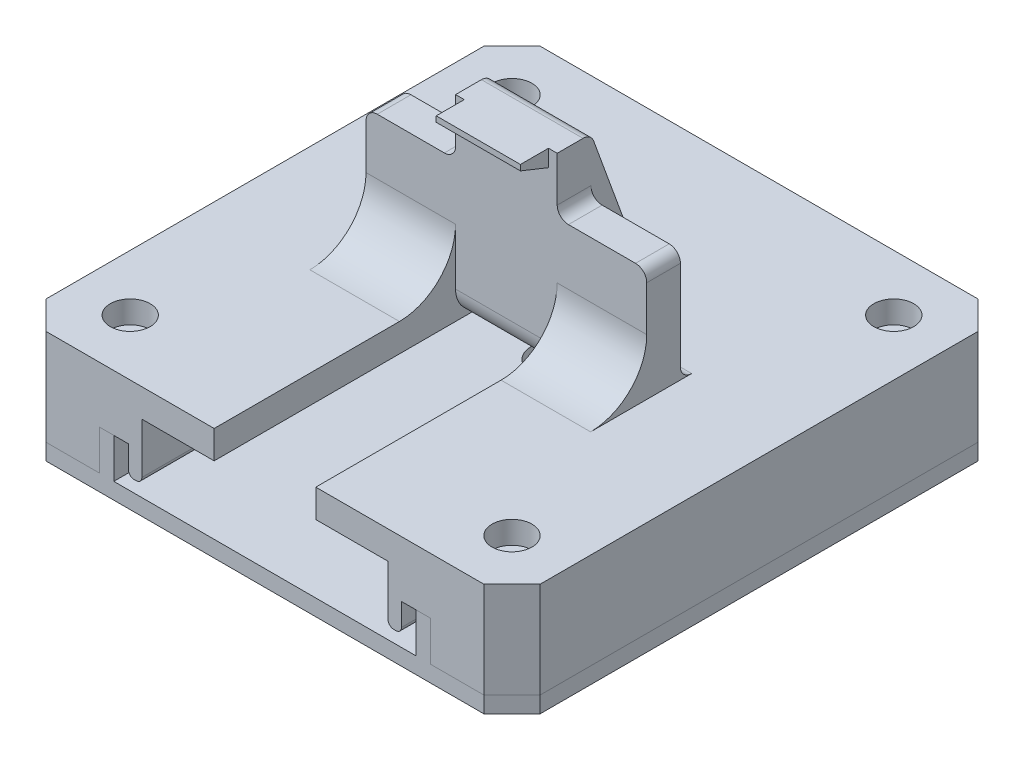
SolidWorks part; units mm, degrees
ref_plane "Piano frontale" through (0, 0, 0) normal (0, 0, 1) x (1, 0, 0)
ref_plane "Piano superiore" through (0, 0, 0) normal (0, 1, 0) x (1, 0, 0)
ref_plane "Piano destro" through (0, 0, 0) normal (1, 0, 0) x (0, 0, -1)
sketch "Schizzo2" plane through (0, 0, 0) normal (0, 1, 0) x (1, 0, 0)
  line L1 (-44, -44) -> (44, -44)
  line L2 (-44, -44) -> (-44, 44)
  line L3 (-44, 44) -> (44, 44)
  line L4 (44, -44) -> (44, 44)
  line L5 (-44, -44) -> (44, 44) construction
  line L6 (-44, 44) -> (44, -44) construction
  point P0 (0, 0)
  dimension "D1" = 88
  dimension "D2" = 88
extrude "Estrusione-Estrusione1" add sketch "Schizzo2" along normal blind 20
sketch "Sketch1" plane through (0, 0, 44) normal (0, 0, 1) x (1, 0, 0)
  line L0 (0, -55) -> (0, 55) construction
  line L1 (-26.925, 15) -> (26.925, 15) construction
  line L2 (-26.925, 15) -> (-26.925, 2.9) construction
  line L3 (-26.925, 2.9) -> (26.925, 2.9)
  line L4 (26.925, 15) -> (26.925, 2.9) construction
  line L5 (-44, 20) -> (44, 20) construction
  line L6 (-26.925, 2.9) -> (-26.925, 10)
  line L7 (-26.925, 10) -> (-24.325, 10)
  line L8 (-24.325, 10) -> (-24.325, 5)
  line L9 (-24.325, 5) -> (-21.925, 5)
  line L10 (-21.925, 5) -> (-21.925, 15)
  line L11 (-21.925, 15) -> (21.925, 15)
  line L12 (26.925, 2.9) -> (26.925, 10)
  line L13 (21.925, 5) -> (21.925, 15)
  line L14 (24.325, 5) -> (21.925, 5)
  line L15 (24.325, 10) -> (24.325, 5)
  line L16 (26.925, 10) -> (24.325, 10)
  point P4 (0, 2.9)
  point P17 (0, 15)
  dimension "D1" = 53.85
  dimension "D2" = 5
  dimension "D3" = 12.1
  dimension "D4" = 2.6
  dimension "D5" = 2.4
  dimension "D6" = 7.1
  dimension "D7" = 2.1
extrude "Cut-Extrude1" cut sketch "Sketch1" against normal through all
sketch "Sketch2" plane through (0, 20, 0) normal (0, 1, 0) x (1, 0, 0)
  line L0 (0, -11) -> (0, 11) construction
  line L1 (-9.05, -1) -> (9.05, -1)
  line L2 (-9.05, -1) -> (-9.05, -75)
  line L3 (-9.05, -75) -> (9.05, -75)
  line L4 (9.05, -1) -> (9.05, -75)
  line L5 (44, 44) -> (-44, 44) construction
  point P4 (0, -1)
  dimension "D1" = 18.1
  dimension "D2" = 45
extrude "Cut-Extrude2" cut sketch "Sketch2" against normal up to next
sketch "Sketch3" plane through (0, 2.9, 0) normal (0, 1, 0) x (1, 0, 0)
  line L0 (0, -11) -> (0, 11) construction
  line L1 (9.05, -1) -> (-9.05, -1) construction
  circle A0 centre (-6.5, 14) radius 4.05
  point P0 (-6.5, 14)
  dimension "D5" = 8.1
  dimension "D1" = 6.5
  dimension "D3" = 15
extrude "Cut-Extrude3" cut sketch "Sketch3" against normal up to next and the other way blind 15
sketch "Sketch9" plane through (0, 2.9, 0) normal (0, 1, 0) x (1, 0, 0)
  line L0 (0, -11) -> (0, 11) construction
  circle A0 centre (6.5, 14) radius 4.05
  circle A2 centre (-6.5, 14) radius 4.05 construction
  point P0 (6.5, 14)
  dimension "D2" = 8.1
  dimension "D1" = 6.5
  dimension "D3" = 0
extrude "Cut-Extrude4" cut sketch "Sketch9" against normal blind 3 and the other way blind 15
sketch "Sketch4" plane through (0, 20, 0) normal (0, 1, 0) x (1, 0, 0)
  line L0 (0, -11) -> (0, 11) construction
  line L1 (-25, -1) -> (25, -1)
  line L2 (-25, -1) -> (-25, 5)
  line L3 (-25, 5) -> (25, 5)
  line L4 (25, -1) -> (25, 5)
  line L5 (9.05, -1) -> (-9.05, -1) construction
  point P5 (0, -1)
  dimension "D1" = 6
  dimension "D2" = 50
extrude "Boss-Extrude1" add sketch "Sketch4" along normal blind 20
sketch "Sketch5" plane through (0, 40, 0) normal (0, 1, 0) x (1, 0, 0)
  line L0 (25, 5) -> (-25, 5) construction
  line L1 (-9.05, -1) -> (9.05, -1)
  line L2 (-9.05, -1) -> (-9.05, 5)
  line L3 (-9.05, 5) -> (9.05, 5)
  line L4 (9.05, -1) -> (9.05, 5)
  line L5 (9.05, -44) -> (9.05, -1) construction
extrude "Boss-Extrude2" add sketch "Sketch5" along normal blind 10
fillet "Fillet1" radius 10 2 edges at (17.025, 20, 1) (-17.025, 20, 1)
sketch "Sketch7" plane through (0, 0, 44) normal (0, 0, 1) x (1, 0, 0)
  line L0 (-44, 10) -> (-24.325, 10) construction
  line L1 (-44, 20) -> (-44, 0) construction
  line L2 (-24.325, 10) -> (-24.325, 5)
  line L3 (-24.325, 5) -> (24.325, 5)
  line L4 (24.325, 5) -> (24.325, 10)
  line L5 (24.325, 10) -> (44, 10) construction
  line L6 (44, 20) -> (44, 0) construction
  line L7 (-29.5, 10) -> (-29.5, 2.9)
  line L8 (-29.5, 2.9) -> (-44, 2.9)
  line L9 (-26.925, 2.9) -> (26.925, 2.9) construction
  line L10 (-29.5, 10) -> (-24.325, 10)
  line L11 (0, -22) -> (0, 22) construction
  line L12 (29.5, 2.9) -> (44, 2.9)
  line L13 (29.5, 10) -> (29.5, 2.9)
  line L14 (24.325, 10) -> (29.5, 10)
  dimension "D1" = 14.5
sketch "Sketch10" plane through (0, 20, 0) normal (0, 1, 0) x (-1, 0, 0)
  line L0 (24.325, 44) -> (-24.325, 44) construction
  line L1 (-34, 34) -> (34, 34) construction
  line L2 (-34, 34) -> (-34, -34) construction
  line L3 (-34, -34) -> (34, -34) construction
  line L4 (34, 34) -> (34, -34) construction
  line L5 (44, -44) -> (44, 44) construction
  line L6 (0, 22) -> (0, -22) construction
  line L7 (22, 0) -> (-22, 0) construction
  point P10 (0, 34)
  point P11 (34, 0)
  point P16 (-34, 34)
  point P19 (34, 34)
  point P22 (34, -34)
  point P25 (-34, -34)
  dimension "D1" = 10
  dimension "D2" = 10
hole_wizard "Ø4.0 (4) Diameter Hole1" positions "Sketch10" profile "Sketch11" hole size "Ø4.0" standard "ISO" end condition up to next
sketch "Sketch11" plane through (34, 20, -34) normal (1, 0, 0) x (0, 0, 1)
  line L0 (0, 0) -> (0, 20)
  line L1 (0, 20) -> (2, 20)
  line L2 (2, 20) -> (2, 0)
  line L5 (2, 0) -> (0, 0)
  line L11 (0, -6.35) -> (0, 107.95) construction
  dimension "Thru Hole Dia." = 4
  dimension "Thru Hole Depth" = 20
sketch "Sketch12" plane through (0, 20, 0) normal (0, 1, 0) x (1, 0, 0)
  line L0 (0, -22) -> (0, 22) construction
  line L2 (-22, 0) -> (22, 0) construction
  circle A0 centre (34, 34) radius 3.55
  circle A1 centre (34, 34) radius 2 construction
  circle A2 centre (-34, 34) radius 3.55
  circle A3 centre (-34, -34) radius 3.55
  circle A4 centre (34, -34) radius 3.55
  dimension "D1" = 7.1
extrude "Cut-Extrude5" cut sketch "Sketch12" against normal blind 4
chamfer "Smusso1" distance 5 angle 45 4 edges at (-44, 10, -44) (-44, 10, 44) (44, 10, 44) (44, 10, -44)
fillet "Raccordo2" radius 2 5 edges at (-25, 40, -2) (25, 40, -2) (0, 20, -5) (-9.05, 40, -2) (9.05, 40, -2)
fillet "Fillet2" radius 1 4 edges at (24.325, 5, 0) (21.925, 5, 0) (-21.925, 5, 0) (-24.325, 5, 0)
sketch "Sketch13" plane through (0, 0, 0) normal (1, 0, 0) x (0, 0, -1)
  line L0 (5, 50) -> (15.9191, 20)
  line L1 (-39, 20) -> (39, 20) construction
  line L2 (15.9191, 20) -> (5, 20)
  line L3 (5, 20) -> (5, 50)
  dimension "D1" = 20
extrude "Boss-Extrude3" add sketch "Sketch13" along normal up to surface and the other way up to surface up to face at (9.05, 46, -2) other way up to face at (-9.05, 46, -2)
fillet "Fillet3" radius 5 1 edges at (0, 15, 1)
fillet "Fillet4" radius 2 1 edges at (0, 50, -5)
sketch "Sketch14" plane through (0, 0, 1) normal (0, 0, 1) x (1, 0, 0)
  line L0 (-9.05, 50) -> (9.05, 50) construction
  line L1 (-7.5, 50) -> (7.5, 50)
  line L2 (-7.5, 50) -> (-7.5, 47)
  line L3 (-7.5, 47) -> (7.5, 47)
  line L4 (7.5, 50) -> (7.5, 47)
  line L6 (0, -22) -> (0, 22) construction
  point P6 (0, 47)
  dimension "D1" = 15
  dimension "D2" = 3
extrude "Boss-Extrude4" add sketch "Sketch14" along normal blind 5
chamfer "Chamfer1" distance 5 distance2 2 1 edges at (0, 47, 6) first distance on face at (0, 47, 3.5)
split "Split1" trim tools "Sketch7" bodies to split 121 resulting bodies 124 125
